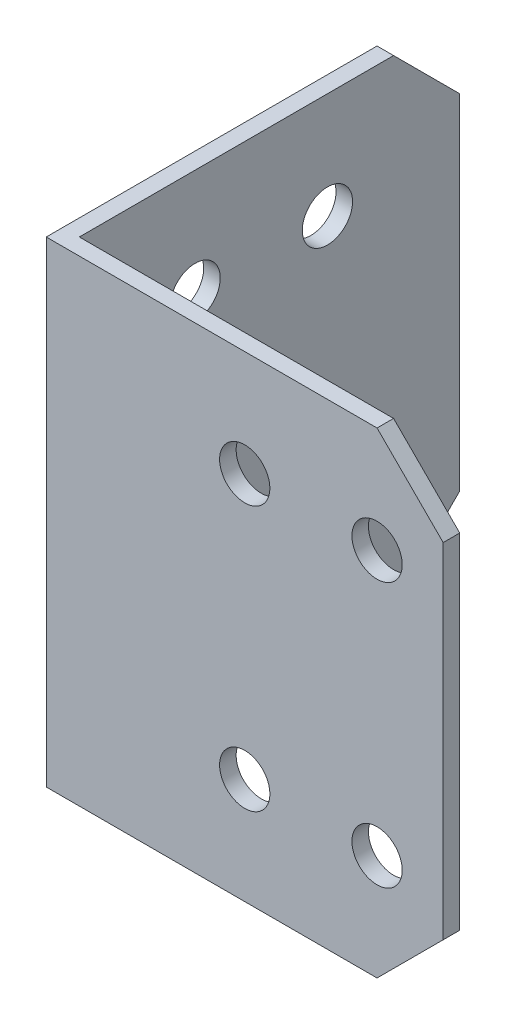
SolidWorks part; units mm, degrees
material "6061-T6 (SS)"
ref_plane "Front Plane" through (0, 0, 0) normal (0, 0, 1) x (1, 0, 0)
ref_plane "Top Plane" through (0, 0, 0) normal (0, 1, 0) x (1, 0, 0)
ref_plane "Right Plane" through (0, 0, 0) normal (1, 0, 0) x (0, 0, -1)
sketch "Sketch1" plane through (0, 0, 0) normal (0, 1, 0) x (1, 0, 0)
  line L1 (-18.1093, 31.6912) -> (-16.5218, 31.6912)
  line L2 (-18.1093, 31.6912) -> (-18.1093, -6.4088)
  line L4 (-16.5218, 31.6912) -> (-16.5218, -4.8213)
  line L5 (-18.1093, -6.4088) -> (19.9907, -6.4088)
  line L7 (-16.5218, -4.8213) -> (19.9907, -4.8213)
  line L8 (19.9907, -6.4088) -> (19.9907, -4.8213)
  point P8 (0, 0)
  dimension "D1" = 1.5875
  dimension "D2" = 1.5875
  dimension "D3" = 38.1
  dimension "D4" = 38.1
extrude "Boss-Extrude1" add sketch "Sketch1" along normal blind 45.72 contours L2 L5 L8 L7 L4 L1
sketch "Sketch2" plane through (0, 0, 4.8213) normal (0, 0, -1) x (-1, 0, 0)
  line L1 (-13.6407, 35.56) -> (-0.9407, 35.56) construction
  line L2 (-13.6407, 35.56) -> (-13.6407, 10.16) construction
  line L3 (-13.6407, 10.16) -> (-0.9407, 10.16) construction
  line L4 (-0.9407, 35.56) -> (-0.9407, 10.16) construction
  line L5 (18.1093, 45.72) -> (18.1093, 0) construction
  line L6 (16.5218, 45.72) -> (-19.9907, 45.72) construction
  circle A0 centre (-0.9407, 35.56) radius 2.413
  circle A1 centre (-13.6407, 35.56) radius 2.413
  circle A2 centre (-13.6407, 10.16) radius 2.413
  circle A3 centre (-0.9407, 10.16) radius 2.413
  dimension "D5" = 4.826
  dimension "D1" = 12.7
  dimension "D2" = 19.05
  dimension "D3" = 10.16
  dimension "D4" = 25.4
extrude "Cut-Extrude1" cut sketch "Sketch2" against normal through all
sketch "Sketch3" plane through (-16.5218, 0, 0) normal (1, 0, 0) x (0, 0, -1)
  line L0 (-6.4088, 45.72) -> (-6.4088, 0) construction
  line L1 (18.9912, 35.56) -> (6.2912, 35.56) construction
  line L2 (18.9912, 35.56) -> (18.9912, 10.16) construction
  line L3 (18.9912, 10.16) -> (6.2912, 10.16) construction
  line L4 (6.2912, 35.56) -> (6.2912, 10.16) construction
  line L5 (31.6912, 45.72) -> (-4.8213, 45.72) construction
  circle A0 centre (6.2912, 35.56) radius 2.413
  circle A1 centre (18.9912, 35.56) radius 2.413
  circle A2 centre (18.9912, 10.16) radius 2.413
  circle A3 centre (6.2912, 10.16) radius 2.413
  dimension "D5" = 4.826
  dimension "D1" = 12.7
  dimension "D2" = 25.4
  dimension "D3" = 10.16
  dimension "D4" = 12.7
extrude "Cut-Extrude2" cut sketch "Sketch3" against normal through all
chamfer "Chamfer1" distance 6.35 angle 45 4 edges at (19.9907, 45.72, 5.615) (19.9907, 0, 5.615) (-17.3155, 0, -31.6912) (-17.3155, 45.72, -31.6912)
